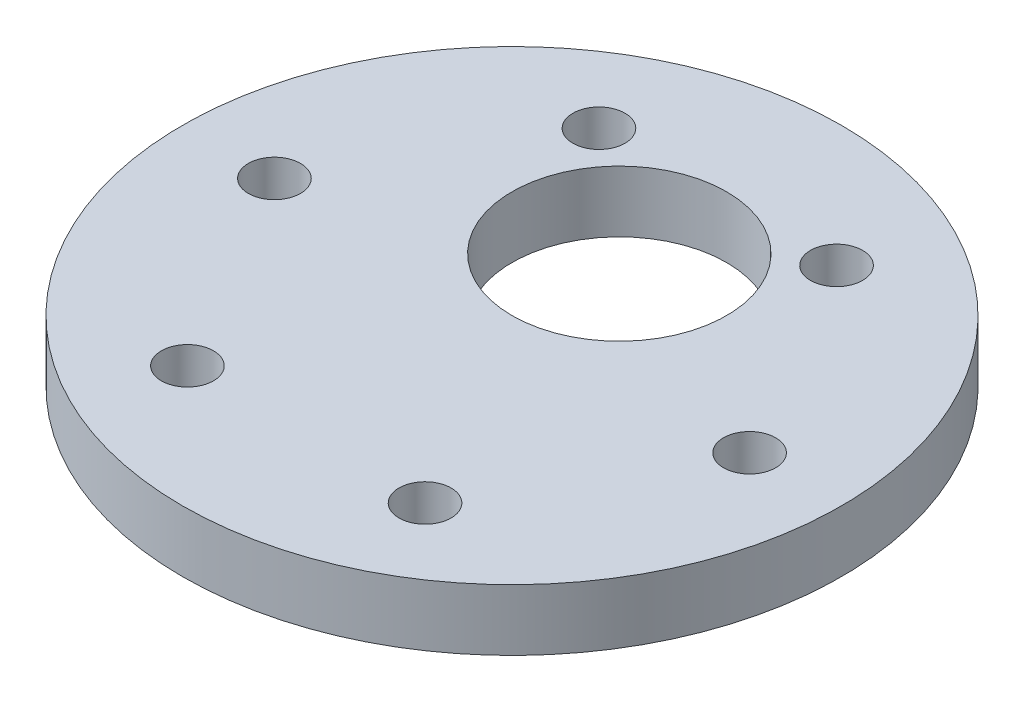
SolidWorks part; units mm, degrees
ref_plane "Front Plane" through (0, 0, 0) normal (0, 0, 1) x (1, 0, 0)
ref_plane "Top Plane" through (0, 0, 0) normal (0, 1, 0) x (1, 0, 0)
ref_plane "Right Plane" through (0, 0, 0) normal (1, 0, 0) x (0, 0, -1)
sketch "Sketch3" plane through (0, 0, 0) normal (0, 1, 0) x (1, 0, 0)
  line L0 (-18.5, 0) -> (18.5, 0) construction
  line L1 (0, 18.5) -> (0, -18.5) construction
  circle A0 centre (0, 0) radius 18.5 construction
  circle A1 centre (0, 0) radius 15.5 construction
  circle A2 centre (-15.5, 0) radius 1.7
  circle A3 centre (0, 7) radius 6 construction
  circle A4 centre (0, 7) radius 7
  circle A5 centre (0, 0) radius 21.5
  dimension "D1" = 37
  dimension "D2" = 31
  dimension "D3" = 3.4
  dimension "D4" = 12
  dimension "D5" = 7
  dimension "D6" = 1
  dimension "D7" = 3
extrude "Boss-Extrude1" add sketch "Sketch3" along normal blind 4 contours A0 A4 A2 | A2 region at (-15.5, 0, 0) region at (0.1092, 0, 0.8359)
extrude "Cut-Extrude2" cut sketch "Sketch3<4>" along normal up to surface (4 mm away) contours A2 region at (-15.5, 0, 0) up to face at (0, 4, 0)
sketch "Sketch3<4>" plane through (0, 0, 0) normal (0, 1, 0) x (1, 0, 0) same geometry as "Sketch3"
pattern_circular "CirPattern1" count 6 every 60 about axis through (0, 4, 0) along (0, 1, 0) of "Cut-Extrude2"
equation "\"motor_face_diam\"= 37mm"
equation "\"motor_screw_holes_diam\"= 31mm"
equation "\"D1@Sketch3\"=\"motor_face_diam\""
equation "\"D2@Sketch3\"=\"motor_screw_holes_diam\""
equation "\"m6_standard fit\"= 6.6mm"
equation "\"motor_face_bracket_thickness\"= 4mm"
equation "\"D1@Boss-Extrude1\"=\"motor_face_bracket_thickness\""
equation "\"motor_braket_cylinder_height\"= \"motor_face_bracket_thickness\" + 22.5 + 28mm"
